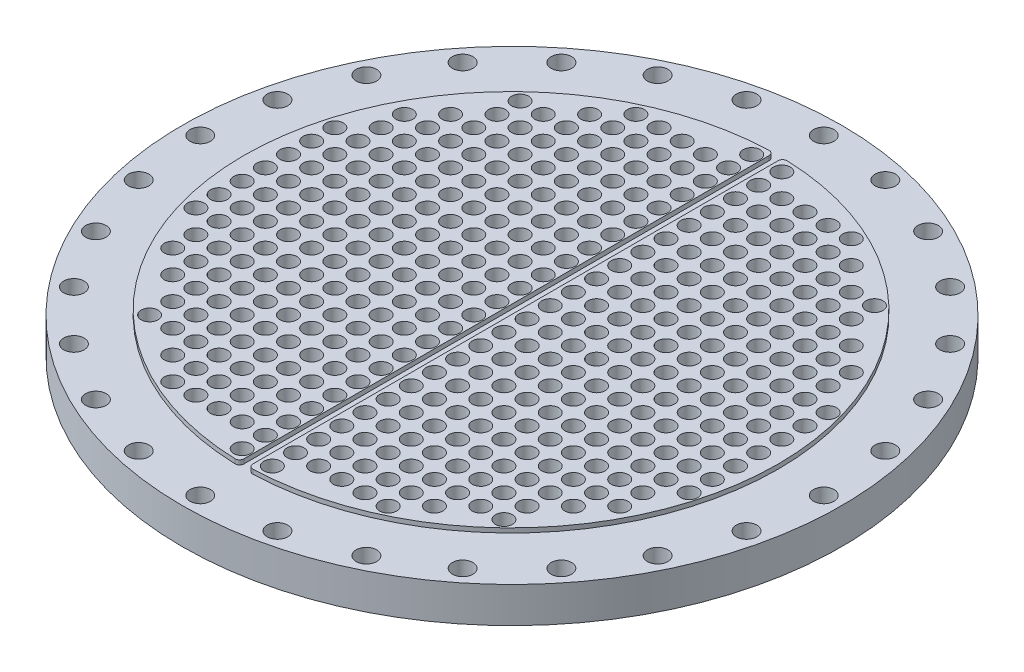
SolidWorks part; units mm, degrees
material " 12Х18Н10Т ГОСТ 4543-71"
ref_plane "Спереди" through (0, 0, 0) normal (0, 0, 1) x (1, 0, 0)
ref_plane "Сверху" through (0, 0, 0) normal (0, 1, 0) x (1, 0, 0)
ref_plane "Справа" through (0, 0, 0) normal (1, 0, 0) x (0, 0, -1)
sketch "Эскиз1" plane through (0, 0, 0) normal (0, 0, 1) x (1, 0, 0)
  line L0 (0, 0) -> (0, 152.1529) construction
  line L1 (-300, 35) -> (-329, 35)
  line L2 (-300, 75) -> (-370, 75)
  line L4 (-300, 35) -> (0, 35)
  line L5 (0, 35) -> (0, 75)
  line L7 (-370, 75) -> (-370, 35)
  line L8 (-370, 35) -> (-329, 35)
  line L11 (0, 75) -> (-300, 75)
  dimension "D1" = 740
  dimension "D2" = 40
revolve "Повернуть1" add sketch "Эскиз1" angle 360 about L0
sketch "Эскиз2" plane through (0, 75, 0) normal (0, 1, 0) x (1, 0, 0)
  circle A0 centre (0, 0) radius 350 construction
  circle A1 centre (0, 350) radius 11.5
  circle A2 centre (77.8823, 341.2248) radius 11.5
  circle A3 centre (151.8593, 315.3391) radius 11.5
  circle A4 centre (218.2214, 273.641) radius 11.5
  circle A5 centre (273.641, 218.2214) radius 11.5
  circle A6 centre (315.3391, 151.8593) radius 11.5
  circle A7 centre (341.2248, 77.8823) radius 11.5
  circle A8 centre (350, 0) radius 11.5
  circle A9 centre (341.2248, -77.8823) radius 11.5
  circle A10 centre (315.3391, -151.8593) radius 11.5
  circle A11 centre (273.641, -218.2214) radius 11.5
  circle A12 centre (218.2214, -273.641) radius 11.5
  circle A13 centre (151.8593, -315.3391) radius 11.5
  circle A14 centre (77.8823, -341.2248) radius 11.5
  circle A15 centre (0, -350) radius 11.5
  circle A16 centre (-77.8823, -341.2248) radius 11.5
  circle A17 centre (-151.8593, -315.3391) radius 11.5
  circle A18 centre (-218.2214, -273.641) radius 11.5
  circle A19 centre (-273.641, -218.2214) radius 11.5
  circle A20 centre (-315.3391, -151.8593) radius 11.5
  circle A21 centre (-341.2248, -77.8823) radius 11.5
  circle A22 centre (-350, 0) radius 11.5
  circle A23 centre (-341.2248, 77.8823) radius 11.5
  circle A24 centre (-315.3391, 151.8593) radius 11.5
  circle A25 centre (-273.641, 218.2214) radius 11.5
  circle A26 centre (-218.2214, 273.641) radius 11.5
  circle A27 centre (-151.8593, 315.3391) radius 11.5
  circle A28 centre (-77.8823, 341.2248) radius 11.5
  point P61 (0, 0)
  dimension "D1" = 700
  dimension "D2" = 23
  dimension "D3" = 28
extrude "Вырез-Вытянуть1" cut sketch "Эскиз2" against normal through all
ref_axis "Ось1" through (-80.9, 0, 0) along (1, 0, 0)
ref_axis "Ось2" through (0, 0, -80.9) along (0, 0, 1)
sketch "Sketch1" plane through (0, 75, 0) normal (0, 1, 0) x (1, 0, 0)
  line L2 (3.9158, 294.8305) -> (3.9158, -294.8305)
  line L4 (-6.0842, 294.8305) -> (-6.0842, -294.8305)
  arc A0 (-11.2537, 299.8276) -> (-11.2537, -299.8276) centre (-1.0842, 0) ccw
  arc A1 (9.0853, -299.8276) -> (9.0853, 299.8276) centre (-1.0842, 0) ccw
  arc A2 (-11.2537, -299.8276) -> (-6.0842, -294.8305) centre (-11.0842, -294.8305) ccw
  arc A3 (3.9158, -294.8305) -> (9.0853, -299.8276) centre (8.9158, -294.8305) ccw
  arc A4 (-6.0842, 294.8305) -> (-11.2537, 299.8276) centre (-11.0842, 294.8305) ccw
  arc A5 (3.9158, 294.8305) -> (9.0853, 299.8276) centre (8.9158, 294.8305) cw
  point P8 (3.9158, -299.9583)
  point P14 (3.9158, 299.9583)
  dimension "D1" = 5
extrude "Boss-Extrude1" add sketch "Sketch1" along normal blind 5
sketch "Sketch2" plane through (0, 80, 0) normal (0, 1, 0) x (1, 0, 0)
  line L0 (3.9158, 0) -> (298.9158, 0) construction
  line L1 (3.9158, 294.8305) -> (3.9158, -294.8305) construction
  line L2 (0, 0) -> (0, -73.9638) construction
  arc A0 (9.0853, -299.8276) -> (9.0853, 299.8276) centre (-1.0842, 0) ccw construction
  circle A1 centre (16.9158, 0) radius 9.525
  circle A2 centre (42.9158, 0) radius 9.525
  circle A3 centre (68.9158, 0) radius 9.525
  circle A4 centre (94.9158, 0) radius 9.525
  circle A5 centre (120.9158, 0) radius 9.525
  circle A6 centre (146.9158, 0) radius 9.525
  circle A7 centre (172.9158, 0) radius 9.525
  circle A8 centre (198.9158, 0) radius 9.525
  circle A9 centre (224.9158, 0) radius 9.525
  circle A10 centre (250.9158, 0) radius 9.525
  circle A11 centre (276.9158, 0) radius 9.525
  circle A12 centre (42.9158, 0) radius 9.525
  circle A13 centre (68.9158, 0) radius 9.525
  circle A14 centre (94.9158, 0) radius 9.525
  circle A15 centre (120.9158, 0) radius 9.525
  circle A16 centre (146.9158, 0) radius 9.525
  circle A17 centre (172.9158, 0) radius 9.525
  circle A18 centre (198.9158, 0) radius 9.525
  circle A19 centre (224.9158, 0) radius 9.525
  circle A20 centre (250.9158, 0) radius 9.525
  circle A21 centre (276.9158, 0) radius 9.525
  circle A22 centre (42.9158, 26) radius 9.525
  circle A23 centre (68.9158, 26) radius 9.525
  circle A24 centre (94.9158, 26) radius 9.525
  circle A25 centre (120.9158, 26) radius 9.525
  circle A26 centre (146.9158, 26) radius 9.525
  circle A27 centre (172.9158, 26) radius 9.525
  circle A28 centre (198.9158, 26) radius 9.525
  circle A29 centre (224.9158, 26) radius 9.525
  circle A30 centre (250.9158, 26) radius 9.525
  circle A31 centre (276.9158, 26) radius 9.525
  circle A32 centre (42.9158, 52) radius 9.525
  circle A33 centre (68.9158, 52) radius 9.525
  circle A34 centre (94.9158, 52) radius 9.525
  circle A35 centre (120.9158, 52) radius 9.525
  circle A36 centre (146.9158, 52) radius 9.525
  circle A37 centre (172.9158, 52) radius 9.525
  circle A38 centre (198.9158, 52) radius 9.525
  circle A39 centre (224.9158, 52) radius 9.525
  circle A40 centre (250.9158, 52) radius 9.525
  circle A41 centre (276.9158, 52) radius 9.525
  circle A42 centre (42.9158, 78) radius 9.525
  circle A43 centre (68.9158, 78) radius 9.525
  circle A44 centre (94.9158, 78) radius 9.525
  circle A45 centre (120.9158, 78) radius 9.525
  circle A46 centre (146.9158, 78) radius 9.525
  circle A47 centre (172.9158, 78) radius 9.525
  circle A48 centre (198.9158, 78) radius 9.525
  circle A49 centre (224.9158, 78) radius 9.525
  circle A50 centre (250.9158, 78) radius 9.525
  circle A51 centre (276.9158, 78) radius 9.525
  circle A52 centre (42.9158, 104) radius 9.525
  circle A53 centre (68.9158, 104) radius 9.525
  circle A54 centre (94.9158, 104) radius 9.525
  circle A55 centre (120.9158, 104) radius 9.525
  circle A56 centre (146.9158, 104) radius 9.525
  circle A57 centre (172.9158, 104) radius 9.525
  circle A58 centre (198.9158, 104) radius 9.525
  circle A59 centre (224.9158, 104) radius 9.525
  circle A60 centre (250.9158, 104) radius 9.525
  circle A61 centre (16.9158, -286) radius 9.525
  circle A62 centre (42.9158, 130) radius 9.525
  circle A63 centre (68.9158, 130) radius 9.525
  circle A64 centre (94.9158, 130) radius 9.525
  circle A65 centre (120.9158, 130) radius 9.525
  circle A66 centre (146.9158, 130) radius 9.525
  circle A67 centre (172.9158, 130) radius 9.525
  circle A68 centre (198.9158, 130) radius 9.525
  circle A69 centre (224.9158, 130) radius 9.525
  circle A70 centre (250.9158, 130) radius 9.525
  circle A71 centre (16.9158, -260) radius 9.525
  circle A72 centre (42.9158, 156) radius 9.525
  circle A73 centre (68.9158, 156) radius 9.525
  circle A74 centre (94.9158, 156) radius 9.525
  circle A75 centre (120.9158, 156) radius 9.525
  circle A76 centre (146.9158, 156) radius 9.525
  circle A77 centre (172.9158, 156) radius 9.525
  circle A78 centre (198.9158, 156) radius 9.525
  circle A79 centre (224.9158, 156) radius 9.525
  circle A80 centre (16.9158, -234) radius 9.525
  circle A81 centre (16.9158, -208) radius 9.525
  circle A82 centre (42.9158, 182) radius 9.525
  circle A83 centre (68.9158, 182) radius 9.525
  circle A84 centre (94.9158, 182) radius 9.525
  circle A85 centre (120.9158, 182) radius 9.525
  circle A86 centre (146.9158, 182) radius 9.525
  circle A87 centre (172.9158, 182) radius 9.525
  circle A88 centre (198.9158, 182) radius 9.525
  circle A89 centre (16.9158, -182) radius 9.525
  circle A90 centre (16.9158, -156) radius 9.525
  circle A91 centre (16.9158, -130) radius 9.525
  circle A92 centre (42.9158, 208) radius 9.525
  circle A93 centre (68.9158, 208) radius 9.525
  circle A94 centre (94.9158, 208) radius 9.525
  circle A95 centre (120.9158, 208) radius 9.525
  circle A96 centre (146.9158, 208) radius 9.525
  circle A97 centre (172.9158, 208) radius 9.525
  circle A98 centre (198.9158, 208) radius 9.525
  circle A99 centre (16.9158, -104) radius 9.525
  circle A100 centre (16.9158, -78) radius 9.525
  circle A101 centre (16.9158, -52) radius 9.525
  circle A102 centre (42.9158, 234) radius 9.525
  circle A103 centre (68.9158, 234) radius 9.525
  circle A104 centre (94.9158, 234) radius 9.525
  circle A105 centre (120.9158, 234) radius 9.525
  circle A106 centre (146.9158, 234) radius 9.525
  circle A107 centre (16.9158, -26) radius 9.525
  circle A108 centre (120.9158, -260) radius 9.525
  circle A109 centre (94.9158, -260) radius 9.525
  circle A110 centre (68.9158, -260) radius 9.525
  circle A111 centre (42.9158, -260) radius 9.525
  circle A112 centre (42.9158, 260) radius 9.525
  circle A113 centre (68.9158, 260) radius 9.525
  circle A114 centre (94.9158, 260) radius 9.525
  circle A115 centre (120.9158, 260) radius 9.525
  circle A116 centre (146.9158, -234) radius 9.525
  circle A117 centre (120.9158, -234) radius 9.525
  circle A118 centre (94.9158, -234) radius 9.525
  circle A119 centre (68.9158, -234) radius 9.525
  circle A120 centre (42.9158, -234) radius 9.525
  circle A121 centre (198.9158, -208) radius 9.525
  circle A122 centre (172.9158, -208) radius 9.525
  circle A123 centre (146.9158, -208) radius 9.525
  circle A124 centre (120.9158, -208) radius 9.525
  circle A125 centre (94.9158, -208) radius 9.525
  circle A126 centre (68.9158, -208) radius 9.525
  circle A127 centre (42.9158, -208) radius 9.525
  circle A128 centre (198.9158, -182) radius 9.525
  circle A129 centre (172.9158, -182) radius 9.525
  circle A130 centre (146.9158, -182) radius 9.525
  circle A131 centre (120.9158, -182) radius 9.525
  circle A132 centre (16.9158, 26) radius 9.525
  circle A133 centre (16.9158, 52) radius 9.525
  circle A134 centre (16.9158, 78) radius 9.525
  circle A135 centre (16.9158, 104) radius 9.525
  circle A136 centre (16.9158, 130) radius 9.525
  circle A137 centre (16.9158, 156) radius 9.525
  circle A138 centre (16.9158, 182) radius 9.525
  circle A139 centre (16.9158, 208) radius 9.525
  circle A140 centre (16.9158, 234) radius 9.525
  circle A141 centre (16.9158, 260) radius 9.525
  circle A142 centre (16.9158, 286) radius 9.525
  circle A143 centre (198.9158, 234) radius 9.525 [skipped]
  circle A144 centre (224.9158, 234) radius 9.525 [skipped]
  circle A145 centre (250.9158, 234) radius 9.525 [skipped]
  circle A146 centre (276.9158, 234) radius 9.525 [skipped]
  circle A147 centre (198.9158, 260) radius 9.525 [skipped]
  circle A148 centre (224.9158, 260) radius 9.525 [skipped]
  circle A149 centre (250.9158, 260) radius 9.525 [skipped]
  circle A150 centre (276.9158, 260) radius 9.525 [skipped]
  circle A151 centre (198.9158, 286) radius 9.525 [skipped]
  circle A152 centre (224.9158, 286) radius 9.525 [skipped]
  circle A153 centre (250.9158, 286) radius 9.525 [skipped]
  circle A154 centre (276.9158, 286) radius 9.525 [skipped]
  circle A155 centre (120.9158, 286) radius 9.525 [skipped]
  circle A156 centre (146.9158, 286) radius 9.525 [skipped]
  circle A157 centre (172.9158, 286) radius 9.525 [skipped]
  circle A158 centre (146.9158, 260) radius 9.525 [skipped]
  circle A159 centre (172.9158, 260) radius 9.525 [skipped]
  circle A160 centre (94.9158, 286) radius 9.525 [skipped]
  circle A161 centre (250.9158, 182) radius 9.525 [skipped]
  circle A162 centre (276.9158, 182) radius 9.525 [skipped]
  circle A163 centre (250.9158, 208) radius 9.525 [skipped]
  circle A164 centre (276.9158, 208) radius 9.525 [skipped]
  circle A165 centre (224.9158, 208) radius 9.525 [skipped]
  circle A166 centre (250.9158, 156) radius 9.525 [skipped]
  circle A167 centre (276.9158, 156) radius 9.525 [skipped]
  circle A168 centre (276.9158, 130) radius 9.525 [skipped]
  circle A169 centre (276.9158, 104) radius 9.525 [skipped]
  circle A170 centre (68.9158, 286) radius 9.525 [skipped]
  circle A171 centre (172.9158, 234) radius 9.525 [skipped]
  circle A172 centre (42.9158, 286) radius 9.525 [skipped]
  circle A173 centre (224.9158, 182) radius 9.525 [skipped]
  circle A174 centre (94.9158, -182) radius 9.525
  circle A175 centre (68.9158, -182) radius 9.525
  circle A176 centre (42.9158, -182) radius 9.525
  circle A177 centre (224.9158, -156) radius 9.525
  circle A178 centre (198.9158, -156) radius 9.525
  circle A179 centre (172.9158, -156) radius 9.525
  circle A180 centre (146.9158, -156) radius 9.525
  circle A181 centre (120.9158, -156) radius 9.525
  circle A182 centre (94.9158, -156) radius 9.525
  circle A183 centre (68.9158, -156) radius 9.525
  circle A184 centre (42.9158, -156) radius 9.525
  circle A185 centre (250.9158, -130) radius 9.525
  circle A186 centre (224.9158, -130) radius 9.525
  circle A187 centre (198.9158, -130) radius 9.525
  circle A188 centre (172.9158, -130) radius 9.525
  circle A189 centre (146.9158, -130) radius 9.525
  circle A190 centre (120.9158, -130) radius 9.525
  circle A191 centre (94.9158, -130) radius 9.525
  circle A192 centre (68.9158, -130) radius 9.525
  circle A193 centre (42.9158, -130) radius 9.525
  circle A194 centre (250.9158, -104) radius 9.525
  circle A195 centre (224.9158, -104) radius 9.525
  circle A196 centre (198.9158, -104) radius 9.525
  circle A197 centre (172.9158, -104) radius 9.525
  circle A198 centre (146.9158, -104) radius 9.525
  circle A199 centre (120.9158, -104) radius 9.525
  circle A200 centre (94.9158, -104) radius 9.525
  circle A201 centre (68.9158, -104) radius 9.525
  circle A202 centre (42.9158, -104) radius 9.525
  circle A203 centre (276.9158, -78) radius 9.525
  circle A204 centre (250.9158, -78) radius 9.525
  circle A205 centre (224.9158, -78) radius 9.525
  circle A206 centre (198.9158, -78) radius 9.525
  circle A207 centre (172.9158, -78) radius 9.525
  circle A208 centre (146.9158, -78) radius 9.525
  circle A209 centre (120.9158, -78) radius 9.525
  circle A210 centre (94.9158, -78) radius 9.525
  circle A211 centre (68.9158, -78) radius 9.525
  circle A212 centre (42.9158, -78) radius 9.525
  circle A213 centre (276.9158, -52) radius 9.525
  circle A214 centre (250.9158, -52) radius 9.525
  circle A215 centre (224.9158, -52) radius 9.525
  circle A216 centre (198.9158, -52) radius 9.525
  circle A217 centre (172.9158, -52) radius 9.525
  circle A218 centre (146.9158, -52) radius 9.525
  circle A219 centre (120.9158, -52) radius 9.525
  circle A220 centre (94.9158, -52) radius 9.525
  circle A221 centre (68.9158, -52) radius 9.525
  circle A222 centre (42.9158, -52) radius 9.525
  circle A223 centre (276.9158, -26) radius 9.525
  circle A224 centre (250.9158, -26) radius 9.525
  circle A225 centre (224.9158, -26) radius 9.525
  circle A226 centre (198.9158, -26) radius 9.525
  circle A227 centre (172.9158, -26) radius 9.525
  circle A228 centre (146.9158, -26) radius 9.525
  circle A229 centre (120.9158, -26) radius 9.525
  circle A230 centre (94.9158, -26) radius 9.525
  circle A231 centre (68.9158, -26) radius 9.525
  circle A232 centre (42.9158, -26) radius 9.525
  circle A233 centre (-42.9158, -26) radius 9.525
  circle A234 centre (-68.9158, -26) radius 9.525
  circle A235 centre (-94.9158, -26) radius 9.525
  circle A236 centre (-120.9158, -26) radius 9.525
  circle A237 centre (-146.9158, -26) radius 9.525
  circle A238 centre (-172.9158, -26) radius 9.525
  circle A239 centre (-198.9158, -26) radius 9.525
  circle A240 centre (-224.9158, -26) radius 9.525
  circle A241 centre (-250.9158, -26) radius 9.525
  circle A242 centre (-276.9158, -26) radius 9.525
  circle A243 centre (-42.9158, -52) radius 9.525
  circle A244 centre (-68.9158, -52) radius 9.525
  circle A245 centre (-94.9158, -52) radius 9.525
  circle A246 centre (-120.9158, -52) radius 9.525
  circle A247 centre (-146.9158, -52) radius 9.525
  circle A248 centre (-172.9158, -52) radius 9.525
  circle A249 centre (-198.9158, -52) radius 9.525
  circle A250 centre (-224.9158, -52) radius 9.525
  circle A251 centre (-250.9158, -52) radius 9.525
  circle A252 centre (-276.9158, -52) radius 9.525
  circle A253 centre (-42.9158, -78) radius 9.525
  circle A254 centre (-68.9158, -78) radius 9.525
  circle A255 centre (-94.9158, -78) radius 9.525
  circle A256 centre (-120.9158, -78) radius 9.525
  circle A257 centre (-146.9158, -78) radius 9.525
  circle A258 centre (-172.9158, -78) radius 9.525
  circle A259 centre (-198.9158, -78) radius 9.525
  circle A260 centre (-224.9158, -78) radius 9.525
  circle A261 centre (-250.9158, -78) radius 9.525
  circle A262 centre (-276.9158, -78) radius 9.525
  circle A263 centre (-42.9158, -104) radius 9.525
  circle A264 centre (-68.9158, -104) radius 9.525
  circle A265 centre (-94.9158, -104) radius 9.525
  circle A266 centre (-120.9158, -104) radius 9.525
  circle A267 centre (-146.9158, -104) radius 9.525
  circle A268 centre (-172.9158, -104) radius 9.525
  circle A269 centre (-198.9158, -104) radius 9.525
  circle A270 centre (-224.9158, -104) radius 9.525
  circle A271 centre (-250.9158, -104) radius 9.525
  circle A272 centre (-42.9158, -130) radius 9.525
  circle A273 centre (-68.9158, -130) radius 9.525
  circle A274 centre (-94.9158, -130) radius 9.525
  circle A275 centre (-120.9158, -130) radius 9.525
  circle A276 centre (-146.9158, -130) radius 9.525
  circle A277 centre (-172.9158, -130) radius 9.525
  circle A278 centre (-198.9158, -130) radius 9.525
  circle A279 centre (-224.9158, -130) radius 9.525
  circle A280 centre (-250.9158, -130) radius 9.525
  circle A281 centre (-42.9158, -156) radius 9.525
  circle A282 centre (-68.9158, -156) radius 9.525
  circle A283 centre (-94.9158, -156) radius 9.525
  circle A284 centre (-120.9158, -156) radius 9.525
  circle A285 centre (-146.9158, -156) radius 9.525
  circle A286 centre (-172.9158, -156) radius 9.525
  circle A287 centre (-198.9158, -156) radius 9.525
  circle A288 centre (-224.9158, -156) radius 9.525
  circle A289 centre (-42.9158, -182) radius 9.525
  circle A290 centre (-68.9158, -182) radius 9.525
  circle A291 centre (-94.9158, -182) radius 9.525
  circle A292 centre (-16.9158, 286) radius 9.525
  circle A293 centre (-16.9158, 260) radius 9.525
  circle A294 centre (-16.9158, 234) radius 9.525
  circle A295 centre (-16.9158, 208) radius 9.525
  circle A296 centre (-16.9158, 182) radius 9.525
  circle A297 centre (-16.9158, 156) radius 9.525
  circle A298 centre (-16.9158, 130) radius 9.525
  circle A299 centre (-16.9158, 104) radius 9.525
  circle A300 centre (-16.9158, 78) radius 9.525
  circle A301 centre (-16.9158, 52) radius 9.525
  circle A302 centre (-16.9158, 26) radius 9.525
  circle A303 centre (-120.9158, -182) radius 9.525
  circle A304 centre (-146.9158, -182) radius 9.525
  circle A305 centre (-172.9158, -182) radius 9.525
  circle A306 centre (-198.9158, -182) radius 9.525
  circle A307 centre (-42.9158, -208) radius 9.525
  circle A308 centre (-68.9158, -208) radius 9.525
  circle A309 centre (-94.9158, -208) radius 9.525
  circle A310 centre (-120.9158, -208) radius 9.525
  circle A311 centre (-146.9158, -208) radius 9.525
  circle A312 centre (-172.9158, -208) radius 9.525
  circle A313 centre (-198.9158, -208) radius 9.525
  circle A314 centre (-42.9158, -234) radius 9.525
  circle A315 centre (-68.9158, -234) radius 9.525
  circle A316 centre (-94.9158, -234) radius 9.525
  circle A317 centre (-120.9158, -234) radius 9.525
  circle A318 centre (-146.9158, -234) radius 9.525
  circle A319 centre (-120.9158, 260) radius 9.525
  circle A320 centre (-94.9158, 260) radius 9.525
  circle A321 centre (-68.9158, 260) radius 9.525
  circle A322 centre (-42.9158, 260) radius 9.525
  circle A323 centre (-42.9158, -260) radius 9.525
  circle A324 centre (-68.9158, -260) radius 9.525
  circle A325 centre (-94.9158, -260) radius 9.525
  circle A326 centre (-120.9158, -260) radius 9.525
  circle A327 centre (-16.9158, -26) radius 9.525
  circle A328 centre (-146.9158, 234) radius 9.525
  circle A329 centre (-120.9158, 234) radius 9.525
  circle A330 centre (-94.9158, 234) radius 9.525
  circle A331 centre (-68.9158, 234) radius 9.525
  circle A332 centre (-42.9158, 234) radius 9.525
  circle A333 centre (-16.9158, -52) radius 9.525
  circle A334 centre (-16.9158, -78) radius 9.525
  circle A335 centre (-16.9158, -104) radius 9.525
  circle A336 centre (-198.9158, 208) radius 9.525
  circle A337 centre (-172.9158, 208) radius 9.525
  circle A338 centre (-146.9158, 208) radius 9.525
  circle A339 centre (-120.9158, 208) radius 9.525
  circle A340 centre (-94.9158, 208) radius 9.525
  circle A341 centre (-68.9158, 208) radius 9.525
  circle A342 centre (-42.9158, 208) radius 9.525
  circle A343 centre (-16.9158, -130) radius 9.525
  circle A344 centre (-16.9158, -156) radius 9.525
  circle A345 centre (-16.9158, -182) radius 9.525
  circle A346 centre (-198.9158, 182) radius 9.525
  circle A347 centre (-172.9158, 182) radius 9.525
  circle A348 centre (-146.9158, 182) radius 9.525
  circle A349 centre (-120.9158, 182) radius 9.525
  circle A350 centre (-94.9158, 182) radius 9.525
  circle A351 centre (-68.9158, 182) radius 9.525
  circle A352 centre (-42.9158, 182) radius 9.525
  circle A353 centre (-16.9158, -208) radius 9.525
  circle A354 centre (-16.9158, -234) radius 9.525
  circle A355 centre (-224.9158, 156) radius 9.525
  circle A356 centre (-198.9158, 156) radius 9.525
  circle A357 centre (-172.9158, 156) radius 9.525
  circle A358 centre (-146.9158, 156) radius 9.525
  circle A359 centre (-120.9158, 156) radius 9.525
  circle A360 centre (-94.9158, 156) radius 9.525
  circle A361 centre (-68.9158, 156) radius 9.525
  circle A362 centre (-42.9158, 156) radius 9.525
  circle A363 centre (-16.9158, -260) radius 9.525
  circle A364 centre (-250.9158, 130) radius 9.525
  circle A365 centre (-224.9158, 130) radius 9.525
  circle A366 centre (-198.9158, 130) radius 9.525
  circle A367 centre (-172.9158, 130) radius 9.525
  circle A368 centre (-146.9158, 130) radius 9.525
  circle A369 centre (-120.9158, 130) radius 9.525
  circle A370 centre (-94.9158, 130) radius 9.525
  circle A371 centre (-68.9158, 130) radius 9.525
  circle A372 centre (-42.9158, 130) radius 9.525
  circle A373 centre (-16.9158, -286) radius 9.525
  circle A374 centre (-250.9158, 104) radius 9.525
  circle A375 centre (-224.9158, 104) radius 9.525
  circle A376 centre (-198.9158, 104) radius 9.525
  circle A377 centre (-172.9158, 104) radius 9.525
  circle A378 centre (-146.9158, 104) radius 9.525
  circle A379 centre (-120.9158, 104) radius 9.525
  circle A380 centre (-94.9158, 104) radius 9.525
  circle A381 centre (-68.9158, 104) radius 9.525
  circle A382 centre (-42.9158, 104) radius 9.525
  circle A383 centre (-276.9158, 78) radius 9.525
  circle A384 centre (-250.9158, 78) radius 9.525
  circle A385 centre (-224.9158, 78) radius 9.525
  circle A386 centre (-198.9158, 78) radius 9.525
  circle A387 centre (-172.9158, 78) radius 9.525
  circle A388 centre (-146.9158, 78) radius 9.525
  circle A389 centre (-120.9158, 78) radius 9.525
  circle A390 centre (-94.9158, 78) radius 9.525
  circle A391 centre (-68.9158, 78) radius 9.525
  circle A392 centre (-42.9158, 78) radius 9.525
  circle A393 centre (-276.9158, 52) radius 9.525
  circle A394 centre (-250.9158, 52) radius 9.525
  circle A395 centre (-224.9158, 52) radius 9.525
  circle A396 centre (-198.9158, 52) radius 9.525
  circle A397 centre (-172.9158, 52) radius 9.525
  circle A398 centre (-146.9158, 52) radius 9.525
  circle A399 centre (-120.9158, 52) radius 9.525
  circle A400 centre (-94.9158, 52) radius 9.525
  circle A401 centre (-68.9158, 52) radius 9.525
  circle A402 centre (-42.9158, 52) radius 9.525
  circle A403 centre (-276.9158, 26) radius 9.525
  circle A404 centre (-250.9158, 26) radius 9.525
  circle A405 centre (-224.9158, 26) radius 9.525
  circle A406 centre (-198.9158, 26) radius 9.525
  circle A407 centre (-172.9158, 26) radius 9.525
  circle A408 centre (-146.9158, 26) radius 9.525
  circle A409 centre (-120.9158, 26) radius 9.525
  circle A410 centre (-94.9158, 26) radius 9.525
  circle A411 centre (-68.9158, 26) radius 9.525
  circle A412 centre (-42.9158, 26) radius 9.525
  circle A413 centre (-276.9158, 0) radius 9.525
  circle A414 centre (-250.9158, 0) radius 9.525
  circle A415 centre (-224.9158, 0) radius 9.525
  circle A416 centre (-198.9158, 0) radius 9.525
  circle A417 centre (-172.9158, 0) radius 9.525
  circle A418 centre (-146.9158, 0) radius 9.525
  circle A419 centre (-120.9158, 0) radius 9.525
  circle A420 centre (-94.9158, 0) radius 9.525
  circle A421 centre (-68.9158, 0) radius 9.525
  circle A422 centre (-42.9158, 0) radius 9.525
  circle A423 centre (-276.9158, 0) radius 9.525
  circle A424 centre (-250.9158, 0) radius 9.525
  circle A425 centre (-224.9158, 0) radius 9.525
  circle A426 centre (-198.9158, 0) radius 9.525
  circle A427 centre (-172.9158, 0) radius 9.525
  circle A428 centre (-146.9158, 0) radius 9.525
  circle A429 centre (-120.9158, 0) radius 9.525
  circle A430 centre (-94.9158, 0) radius 9.525
  circle A431 centre (-68.9158, 0) radius 9.525
  circle A432 centre (-42.9158, 0) radius 9.525
  circle A433 centre (-16.9158, 0) radius 9.525
  dimension "D1" = 13
  dimension "D2" = 11
  dimension "D3" = 11
  dimension "D4" = 12
extrude "Cut-Extrude1" cut sketch "Sketch2" against normal through all
